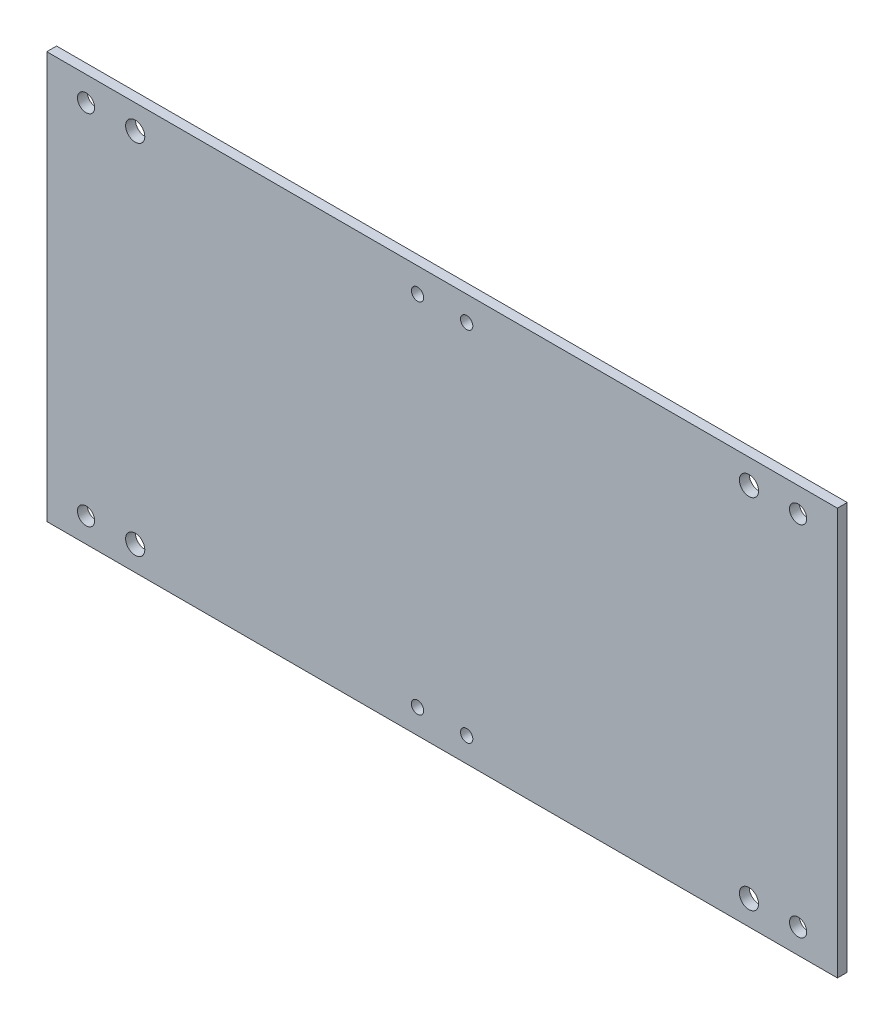
SolidWorks part; units mm, degrees
ref_plane "Front Plane" through (0, 0, 0) normal (0, 0, 1) x (1, 0, 0)
ref_plane "Top Plane" through (0, 0, 0) normal (0, 1, 0) x (1, 0, 0)
ref_plane "Right Plane" through (0, 0, 0) normal (1, 0, 0) x (0, 0, -1)
sketch "Sketch1" plane through (0, 0, 0) normal (0, 0, 1) x (1, 0, 0)
  line L0 (591.9925, 431.4754) -> (591.9925, 265.8654) construction
  line L1 (431.0875, 431.4754) -> (752.8975, 431.4754)
  line L2 (431.0875, 431.4754) -> (431.0875, 265.8654)
  line L3 (431.0875, 265.8654) -> (752.8975, 265.8654)
  line L4 (752.8975, 431.4754) -> (752.8975, 265.8654)
  dimension "D1" = 321.81
  dimension "D2" = 165.61
extrude "Boss-Extrude1" add sketch "Sketch1" along normal blind 4
sketch "Sketch3" plane through (0, 0, 4) normal (0, 0, 1) x (1, 0, 0)
  line L0 (752.8975, 431.4754) -> (431.0875, 431.4754) construction
  line L1 (431.0875, 265.8654) -> (752.8975, 265.8654) construction
  line L2 (431.0875, 431.4754) -> (431.0875, 265.8654) construction
  line L3 (752.8975, 265.8654) -> (752.8975, 431.4754) construction
  circle A0 centre (447.0875, 421.4754) radius 3.5
  circle A1 centre (736.8975, 421.4754) radius 3.5
  circle A2 centre (736.8975, 275.8654) radius 3.5
  circle A3 centre (447.0875, 275.8654) radius 3.5
  dimension "D1" = 7
  dimension "D2" = 7
  dimension "D3" = 7
  dimension "D4" = 7
  dimension "D5" = 10
  dimension "D6" = 10
  dimension "D7" = 16
  dimension "D8" = 16
extrude "Cut-Extrude1" cut sketch "Sketch3" against normal through all
sketch "Sketch4" plane through (0, 0, 4) normal (0, 0, 1) x (1, 0, 0)
  circle A0 centre (467.0875, 421.4754) radius 3.9
  circle A1 centre (716.8975, 421.4754) radius 3.9
  circle A2 centre (716.8975, 275.8654) radius 3.9
  circle A3 centre (467.0875, 275.8654) radius 3.9
  circle A5 centre (736.8975, 421.4754) radius 3.5 construction
  point P8 (447.0875, 421.4754)
  point P9 (447.0875, 275.8654)
  dimension "D1" = 7.8
  dimension "D2" = 7.8
  dimension "D3" = 7.8
  dimension "D4" = 7.8
  dimension "D7" = 20
  dimension "D5" = 20
extrude "Cut-Extrude2" cut sketch "Sketch4" against normal blind 10
sketch "Sketch5" plane through (0, 0, 4) normal (0, 0, 1) x (1, 0, 0)
  line L0 (581.9925, 421.4754) -> (601.9925, 421.4754) construction
  line L1 (591.9925, 431.4754) -> (591.9925, 265.8654) construction
  line L2 (431.0875, 265.8654) -> (752.8975, 265.8654) construction
  line L3 (752.8975, 431.4754) -> (431.0875, 431.4754) construction
  circle A0 centre (581.9925, 421.4754) radius 2.5
  circle A1 centre (601.9925, 421.4754) radius 2.5
  circle A2 centre (581.9925, 275.8654) radius 2.5
  circle A3 centre (601.9925, 275.8654) radius 2.5
  point P2 (591.9925, 421.4754)
  dimension "D6" = 10
  dimension "D1" = 5
  dimension "D2" = 5
  dimension "D4" = 5
  dimension "D5" = 5
  dimension "D3" = 20
  dimension "D7" = 10
extrude "Cut-Extrude4" cut sketch "Sketch5" against normal blind 10
sketch "Sketch6" [suppressed] plane through (0, 0, 4) normal (0, 0, 1) x (1, 0, 0)
  line L0 (447.0875, 431.4754) -> (752.8975, 431.4754) construction
  line L1 (447.0875, 265.8654) -> (752.8975, 265.8654) construction
  line L2 (594.4925, 426.4754) -> (605.4925, 426.4754) construction
  line L3 (599.9925, 431.4754) -> (599.9925, 265.8654) construction
  circle A0 centre (594.4925, 426.4754) radius 1.5
  circle A1 centre (605.4925, 426.4754) radius 1.5
  circle A2 centre (594.4925, 270.8654) radius 1.5
  circle A3 centre (605.4925, 270.8654) radius 1.5
  point P12 (599.9925, 426.4754)
  dimension "D1" = 5
  dimension "D3" = 3
  dimension "D4" = 3
  dimension "D5" = 3
  dimension "D6" = 3
  dimension "D2" = 11
  dimension "D7" = 5
extrude "Cut-Extrude5" [suppressed] cut sketch "Sketch6" against normal blind 10
fillet "Fillet1" [suppressed] radius 2
equation "\"D2@Sketch4\"=\"D1@Sketch4\""
equation "\"D3@Sketch4\"=\"D1@Sketch4\""
equation "\"D4@Sketch4\"=\"D1@Sketch4\""
equation "\"D7@Sketch4\"=\"D5@Sketch4\""
equation "\"D2@Sketch3\"=\"D1@Sketch3\""
equation "\"D3@Sketch3\"=\"D1@Sketch3\""
equation "\"D4@Sketch3\"=\"D1@Sketch3\""
equation "\"D6@Sketch3\"=\"D5@Sketch3\""
equation "\"D8@Sketch3\"=\"D7@Sketch3\""
equation "\"D4@Sketch5\"=\"D1@Sketch5\""
equation "\"D5@Sketch5\"=\"D1@Sketch5\""
equation "\"D2@Sketch5\"=\"D1@Sketch5\""
equation "\"D6@Sketch5\"=\"D7@Sketch5\""
equation "\"D4@Sketch6\"=\"D3@Sketch6\""
equation "\"D5@Sketch6\"=\"D3@Sketch6\""
equation "\"D6@Sketch6\"=\"D3@Sketch6\""
equation "\"D7@Sketch6\"=\"D1@Sketch6\""
